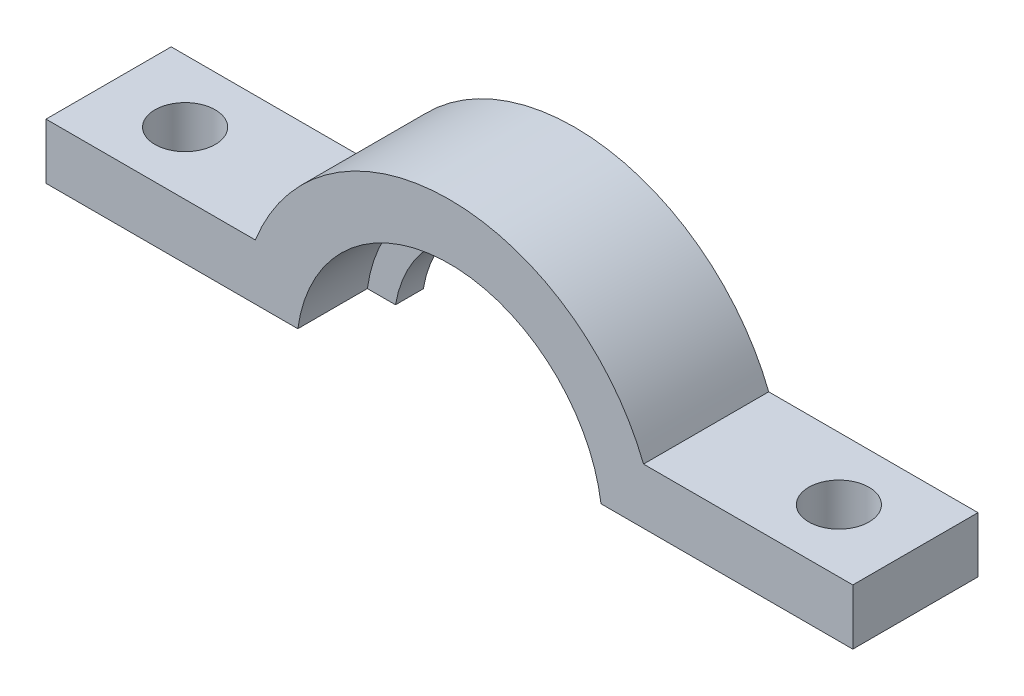
SolidWorks part; units mm, degrees
ref_plane "Front Plane" through (0, 0, 0) normal (0, 0, 1) x (1, 0, 0)
ref_plane "Top Plane" through (0, 0, 0) normal (0, 1, 0) x (1, 0, 0)
ref_plane "Right Plane" through (0, 0, 0) normal (1, 0, 0) x (0, 0, -1)
sketch "Sketch1" plane through (0, 0, 0) normal (0, 0, 1) x (1, 0, 0)
  line L0 (18.0566, -9.075) -> (-0.8028, 0.4035) construction
  line L2 (29, -13.075) -> (29, -9.075)
  line L4 (-29, -13.075) -> (-29, -9.075)
  line L5 (26.0154, -13.075) -> (24.2978, -12.2117) construction
  line L10 (-29, -13.075) -> (-10.8972, -13.075)
  line L11 (29, -13.075) -> (10.8972, -13.075)
  line L12 (-29, -9.075) -> (-13.9553, -9.075)
  line L13 (13.9553, -9.075) -> (29, -9.075)
  line L15 (-23.5, -11.8108) -> (-29, -14.575) construction
  line L18 (0.8028, 0.4035) -> (-18.0566, -9.075) construction
  arc A0 (10.8972, -13.075) -> (-10.8972, -13.075) centre (0, -14.575) ccw
  arc A1 (13.9553, -9.075) -> (-13.9553, -9.075) centre (0, -14.575) ccw
  point P1 (0, 0)
  dimension "D4" = 22
  dimension "D6" = 30
  dimension "D7" = 4
extrude "Boss-Extrude1" add sketch "Sketch1" along normal blind 9
sketch "Sketch2" plane through (0, -9.075, 0) normal (0, 1, 0) x (1, 0, 0)
  line L0 (-23.5, -4.5) -> (23.5, -4.5) construction
  line L1 (-29, -9) -> (-29, 0) construction
  line L2 (-23.5, -4.5) -> (-29, -4.5) construction
  line L3 (23.5, -4.5) -> (29, -4.5) construction
  line L4 (29, -9) -> (29, 0) construction
  line L5 (-23.5, 0) -> (-23.5, -4.5) construction
  line L6 (-13.9553, 0) -> (-29, 0) construction
  line L7 (-23.5, -4.5) -> (-23.5, -9) construction
  line L8 (-13.9553, -9) -> (-29, -9) construction
  circle A0 centre (-23.5, -4.5) radius 2.165
  circle A1 centre (23.5, -4.5) radius 2.165
  dimension "D1" = 47
extrude "Cut-Extrude1" cut sketch "Sketch2" against normal through all
ref_plane "Plane1" through (0, 0, 2) normal (0, 0, -1) x (-1, 0, 0)
sketch "Sketch3" plane through (0, 0, 2) normal (0, 0, -1) x (-1, 0, 0)
  line L0 (-10.8972, -13.075) -> (-8.8741, -13.075)
  line L1 (8.8741, -13.075) -> (10.8972, -13.075)
  arc A0 (10.8972, -13.075) -> (-10.8972, -13.075) centre (0, -14.575) ccw
  arc A1 (10.8972, -13.075) -> (-10.8972, -13.075) centre (0, -14.575) ccw construction
  arc A2 (8.8741, -13.075) -> (-8.8741, -13.075) centre (0, -14.575) ccw
  dimension "D1" = 2
extrude "Boss-Extrude2" add sketch "Sketch3" against normal blind 2
